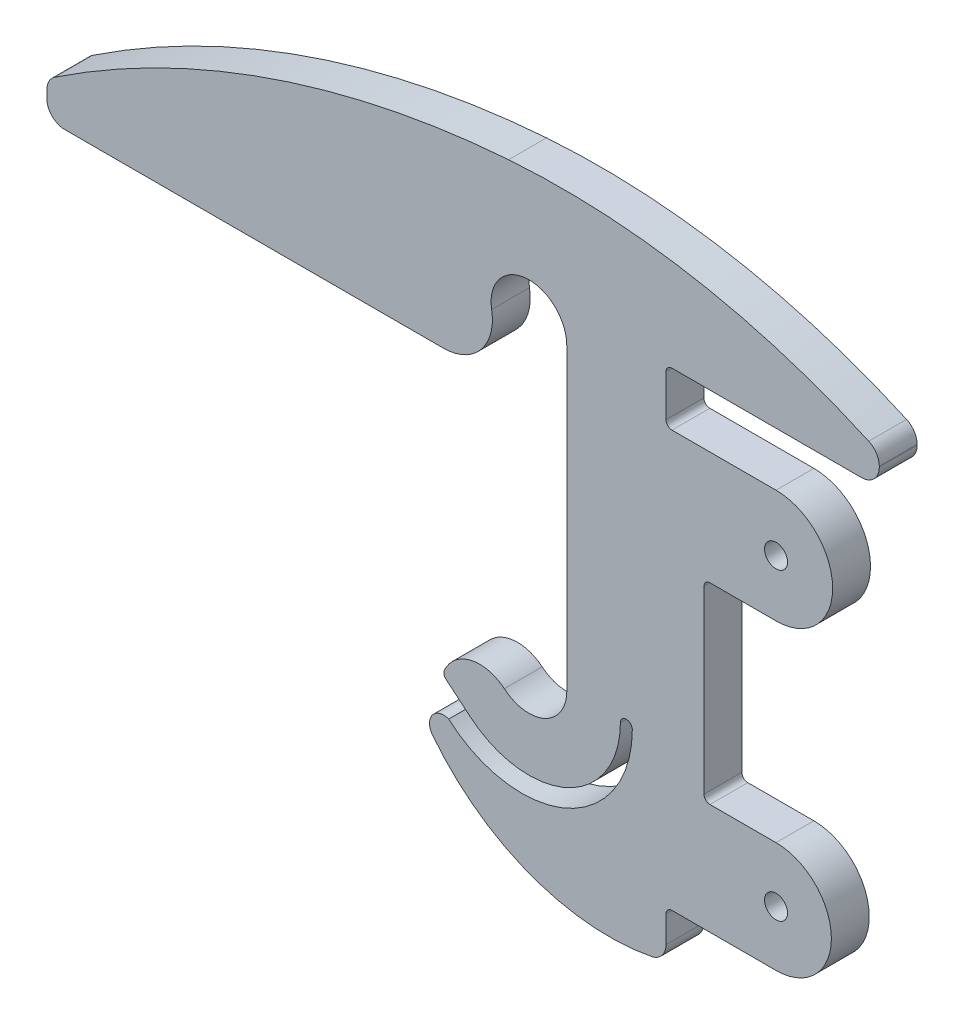
SolidWorks part; units mm, degrees
ref_plane "Front Plane" through (0, 0, 0) normal (0, 0, 1) x (1, 0, 0)
ref_plane "Top Plane" through (0, 0, 0) normal (0, 1, 0) x (1, 0, 0)
ref_plane "Right Plane" through (0, 0, 0) normal (1, 0, 0) x (0, 0, -1)
sketch "Model" plane through (0, 0, 0) normal (0, 0, 1) x (1, 0, 0)
  line L0 (14.6829, 1.325) -> (14.6829, -14.782)
  line L2 (29.3928, 17.8652) -> (29.3928, 15.325)
  line L3 (29.3928, 15.325) -> (11.5, 15.325)
  line L4 (11.5, 10.825) -> (11.5, 15.325)
  line L5 (20.7299, 10.825) -> (11.5, 10.825)
  line L6 (20.7299, 1.325) -> (14.6829, 1.325)
  line L7 (14.6829, -14.782) -> (20.7299, -14.782)
  line L8 (20.7299, -24.0681) -> (11.5, -24.0681)
  line L9 (15.2057, -14.282) -> (26.7057, -14.282) construction
  line L10 (11.5, -28.0042) -> (11.5, -24.0681)
  line L30 (-40.4406, 9.3328) -> (-40.4406, 8.6908)
  line L31 (-38.9406, 7.1908) -> (-7.182, 7.1908)
  line L32 (3.175, 12.575) -> (3.175, -12.575)
  line L33 (-7.2315, -16.526) -> (-4.9334, -18.4544)
  arc A0 (-1.7042, 23.6193) -> (29.3928, 17.8652) centre (2.8223, -38.8245) cw
  arc A1 (20.7299, 10.825) -> (20.7299, 1.325) centre (20.7299, 6.075) cw
  arc A2 (20.7299, -14.782) -> (20.7299, -24.0681) centre (20.7299, -19.425) cw
  arc A3 (-8.0912, -21.3717) -> (11.5, -28.0042) centre (6.7381, -9.8191) ccw
  arc A4 (3.175, -12.575) -> (-2.0615, -14.9897) centre (0, -12.575) cw
  arc A5 (-4.9334, -18.4544) -> (7.675, -12.5941) centre (0, -12.575) ccw
  arc A6 (7.675, -12.5941) -> (8.675, -12.5954) centre (8.175, -12.5954) cw
  arc A7 (8.675, -12.5954) -> (-6.7315, -19.5356) centre (-0.5917, -12.5948) cw
  arc A8 (-8.0912, -21.3717) -> (-6.7315, -19.5356) centre (-7.1557, -20.643) cw
  arc A21 (-1.7042, 23.6193) -> (-39.7721, 10.5812) centre (4.0052, -55.1441) ccw
  arc A22 (-39.7721, 10.5812) -> (-40.4406, 9.3328) centre (-38.9406, 9.3328) ccw
  arc A23 (-40.4406, 8.6908) -> (-38.9406, 7.1908) centre (-38.9406, 8.6908) ccw
  arc A24 (-7.182, 7.1908) -> (-3.1268, 12.0237) centre (-7.182, 11.3086) ccw
  arc A25 (3.175, 12.575) -> (-3.1268, 12.0237) centre (0, 12.575) ccw
  arc A27 (-2.0615, -14.9897) -> (-7.2315, -16.526) centre (-4.1298, -17.4966) ccw
  dimension "D1" = 11.5
  dimension "D6" = 0.5
  dimension "D2" = 0.5
extrude "Boss-Extrude1" add sketch "Model" along normal blind 3.175
fillet "Fillet1" radius 0.5 6 edges at (-7.2315, -16.526, 1.5875) (11.5, 10.825, 1.5875) (11.5, 15.325, 1.5875) (14.6829, 1.325, 1.5875) (14.6829, -14.782, 1.5875) (11.5, -24.0681, 1.5875)
sketch "Sketch3" plane through (0, 0, 0) normal (0, 0, -1) x (-1, 0, 0)
  circle A0 centre (-20.7299, 6.075) radius 0.9652
  circle A1 centre (-20.7299, -19.425) radius 0.9652
extrude "Cut-Extrude2" [suppressed] cut sketch "Sketch3" against normal up to next
fillet "Fillet2" radius 1.5 3 edges at (29.3928, 15.325, 1.5875) (29.3928, 17.8652, 1.5875) (11.5, -28.0042, 1.5875)
sketch "Sketch4" plane through (0, 0, 3.175) normal (0, 0, 1) x (1, 0, 0)
  circle A0 centre (20.7299, 6.075) radius 0.9652
  circle A1 centre (20.7299, -19.425) radius 0.9652
  dimension "D1" = 1.9304
extrude "Cut-Extrude3" cut sketch "Sketch4" against normal up to next
sketch "final cutout with tabs" plane through (0, 0, 0) normal (0, 0, -1) x (-1, 0, 0)
  line L0 (25.1695, 7.1908) -> (38.9406, 7.1908)
  line L1 (-14.6829, -8.7819) -> (-14.6829, -14.282)
  line L13 (-11.5, -24.5681) -> (-11.5, -26.807)
  line L14 (4.9334, -18.4544) -> (6.9602, -16.7537)
  line L15 (-3.175, -12.575) -> (-3.175, 12.575)
  line L16 (7.182, 7.1908) -> (38.9406, 7.1908)
  line L17 (40.4406, 8.6908) -> (40.4406, 9.3328)
  line L18 (-29.3928, 16.9035) -> (-29.3928, 16.825)
  line L19 (-27.8928, 15.325) -> (-12, 15.325)
  line L20 (-11.5, 14.825) -> (-11.5, 11.325)
  line L21 (-12, 10.825) -> (-20.7299, 10.825)
  line L22 (-20.7299, 1.325) -> (-15.1829, 1.325)
  line L23 (-14.6829, 0.825) -> (-14.6829, -14.282)
  line L24 (-15.1829, -14.782) -> (-20.7299, -14.782)
  line L25 (-20.7299, -24.0681) -> (-12, -24.0681)
  line L26 (-11.5, -24.5681) -> (-11.5, -26.807)
  line L27 (4.9334, -18.4544) -> (6.9602, -16.7537)
  line L28 (-3.175, -12.575) -> (-3.175, 12.575)
  line L29 (7.182, 7.1908) -> (20.9531, 7.1908)
  line L30 (40.4406, 8.6908) -> (40.4406, 9.3328)
  line L31 (-29.3928, 16.9035) -> (-29.3928, 16.825)
  line L32 (-27.8928, 15.325) -> (-12, 15.325)
  line L33 (-11.5, 14.825) -> (-11.5, 11.325)
  line L34 (-12, 10.825) -> (-20.7299, 10.825)
  line L35 (-20.7299, 1.325) -> (-15.1829, 1.325)
  line L36 (-14.6829, 0.825) -> (-14.6829, -4.6751)
  line L37 (-15.1829, -14.782) -> (-20.7299, -14.782)
  line L38 (-20.7299, -24.0681) -> (-12, -24.0681)
  arc A0 (1.7285, -26.6027) -> (8.0912, -21.3717) centre (-6.7381, -9.8191) ccw
  arc A4 (9.9687, 22.5798) -> (1.7042, 23.6193) centre (-4.0052, -55.1441) ccw
  arc A24 (-11.5, -26.807) -> (-10.2829, -28.28) centre (-10, -26.807) ccw
  arc A25 (-10.2829, -28.28) -> (8.0912, -21.3717) centre (-6.7381, -9.8191) ccw
  arc A26 (8.0912, -21.3717) -> (6.7315, -19.5356) centre (7.1557, -20.643) ccw
  arc A27 (-8.675, -12.5954) -> (6.7315, -19.5356) centre (0.5917, -12.5948) ccw
  arc A28 (-7.675, -12.5941) -> (-8.675, -12.5954) centre (-8.175, -12.5954) ccw
  arc A29 (-7.675, -12.5941) -> (4.9334, -18.4544) centre (0, -12.575) ccw
  arc A30 (6.9602, -16.7537) -> (7.095, -16.166) centre (6.6388, -16.3707) ccw
  arc A31 (7.095, -16.166) -> (2.0615, -14.9897) centre (4.1298, -17.4966) ccw
  arc A32 (-3.175, -12.575) -> (2.0615, -14.9897) centre (0, -12.575) ccw
  arc A33 (3.1268, 12.0237) -> (-3.175, 12.575) centre (0, 12.575) ccw
  arc A34 (3.1268, 12.0237) -> (7.182, 7.1908) centre (7.182, 11.3086) ccw
  arc A35 (38.9406, 7.1908) -> (40.4406, 8.6908) centre (38.9406, 8.6908) ccw
  arc A36 (40.4406, 9.3328) -> (39.7721, 10.5812) centre (38.9406, 9.3328) ccw
  arc A37 (39.7721, 10.5812) -> (1.7042, 23.6193) centre (-4.0052, -55.1441) ccw
  arc A38 (1.7042, 23.6193) -> (-28.5082, 18.2715) centre (-2.8223, -38.8245) ccw
  arc A39 (-28.5082, 18.2715) -> (-29.3928, 16.9035) centre (-27.8928, 16.9035) ccw
  arc A40 (-29.3928, 16.825) -> (-27.8928, 15.325) centre (-27.8928, 16.825) ccw
  arc A41 (-11.5, 14.825) -> (-12, 15.325) centre (-12, 14.825) ccw
  arc A42 (-12, 10.825) -> (-11.5, 11.325) centre (-12, 11.325) ccw
  arc A43 (-20.7299, 10.825) -> (-20.7299, 1.325) centre (-20.7299, 6.075) ccw
  arc A44 (-14.6829, 0.825) -> (-15.1829, 1.325) centre (-15.1829, 0.825) ccw
  arc A45 (-15.1829, -14.782) -> (-14.6829, -14.282) centre (-15.1829, -14.282) ccw
  arc A46 (-20.7299, -14.782) -> (-20.7299, -24.0681) centre (-20.7299, -19.425) ccw
  arc A47 (-11.5, -24.5681) -> (-12, -24.0681) centre (-12, -24.5681) ccw
  arc A48 (-11.5, -26.807) -> (-10.2829, -28.28) centre (-10, -26.807) ccw
  arc A49 (-10.2829, -28.28) -> (-2.05, -28.0233) centre (-6.7381, -9.8191) ccw
  arc A50 (8.0912, -21.3717) -> (6.7315, -19.5356) centre (7.1557, -20.643) ccw
  arc A51 (-8.675, -12.5954) -> (6.7315, -19.5356) centre (0.5917, -12.5948) ccw
  arc A52 (-7.675, -12.5941) -> (-8.675, -12.5954) centre (-8.175, -12.5954) ccw
  arc A53 (-7.675, -12.5941) -> (4.9334, -18.4544) centre (0, -12.575) ccw
  arc A54 (6.9602, -16.7537) -> (7.095, -16.166) centre (6.6388, -16.3707) ccw
  arc A55 (7.095, -16.166) -> (2.0615, -14.9897) centre (4.1298, -17.4966) ccw
  arc A56 (-3.175, -12.575) -> (2.0615, -14.9897) centre (0, -12.575) ccw
  arc A57 (3.1268, 12.0237) -> (-3.175, 12.575) centre (0, 12.575) ccw
  arc A58 (3.1268, 12.0237) -> (7.182, 7.1908) centre (7.182, 11.3086) ccw
  arc A59 (38.9406, 7.1908) -> (40.4406, 8.6908) centre (38.9406, 8.6908) ccw
  arc A60 (40.4406, 9.3328) -> (39.7721, 10.5812) centre (38.9406, 9.3328) ccw
  arc A61 (39.7721, 10.5812) -> (13.896, 21.7702) centre (-4.0052, -55.1441) ccw
  arc A62 (1.7042, 23.6193) -> (-28.5082, 18.2715) centre (-2.8223, -38.8245) ccw
  arc A63 (-28.5082, 18.2715) -> (-29.3928, 16.9035) centre (-27.8928, 16.9035) ccw
  arc A64 (-29.3928, 16.825) -> (-27.8928, 15.325) centre (-27.8928, 16.825) ccw
  arc A65 (-11.5, 14.825) -> (-12, 15.325) centre (-12, 14.825) ccw
  arc A66 (-12, 10.825) -> (-11.5, 11.325) centre (-12, 11.325) ccw
  arc A67 (-20.7299, 10.825) -> (-20.7299, 1.325) centre (-20.7299, 6.075) ccw
  arc A68 (-14.6829, 0.825) -> (-15.1829, 1.325) centre (-15.1829, 0.825) ccw
  arc A69 (-15.1829, -14.782) -> (-14.6829, -14.282) centre (-15.1829, -14.282) ccw
  arc A70 (-20.7299, -14.782) -> (-20.7299, -24.0681) centre (-20.7299, -19.425) ccw
  arc A71 (-11.5, -24.5681) -> (-12, -24.0681) centre (-12, -24.5681) ccw
  dimension "D1" = 0
